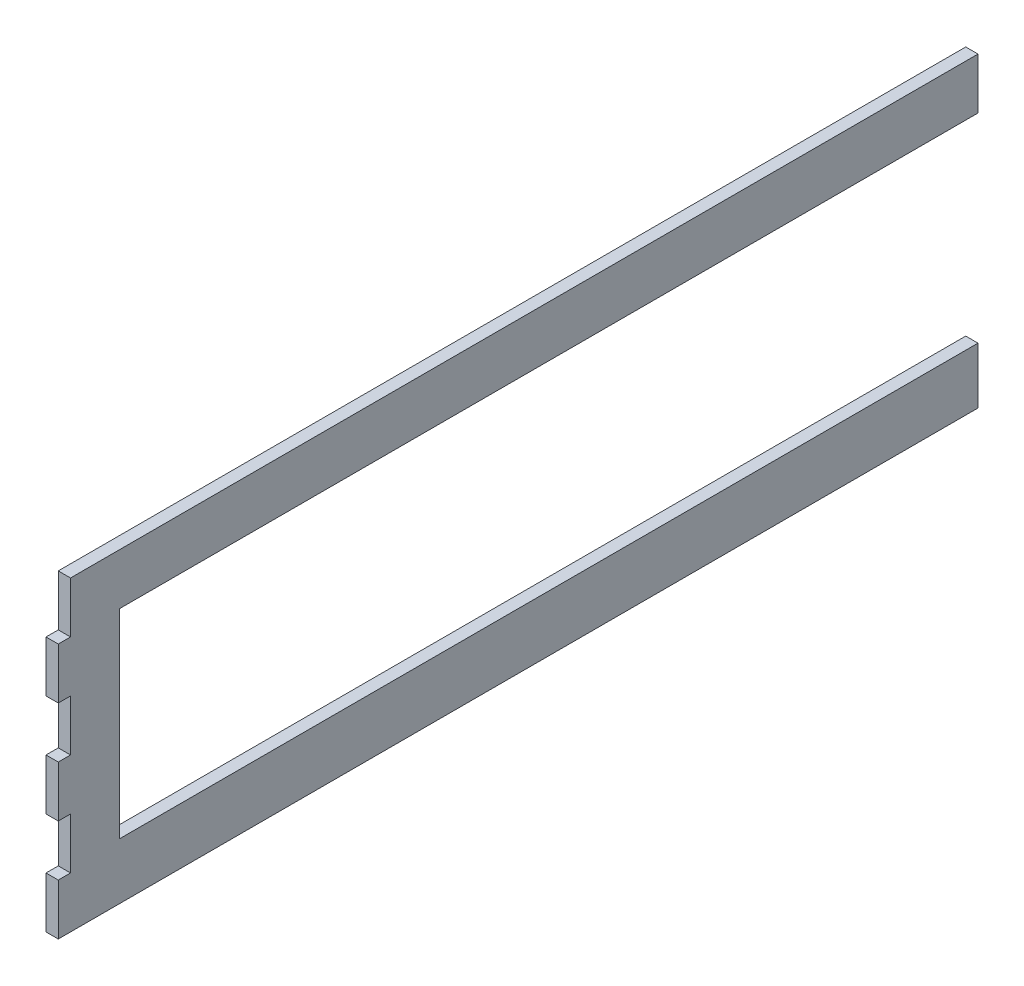
SolidWorks part; units mm, degrees
ref_plane "Front" through (0, 0, 0) normal (0, 0, 1) x (1, 0, 0)
ref_plane "Top" through (0, 0, 0) normal (0, 1, 0) x (1, 0, 0)
ref_plane "Right" through (0, 0, 0) normal (1, 0, 0) x (0, 0, -1)
sketch "Sketch1" plane through (0, 0, 0) normal (1, 0, 0) x (0, 0, -1)
  line L0 (450, 125) -> (450, 150)
  line L1 (0, 0) -> (450, 0)
  line L2 (0, 0) -> (0, 150)
  line L3 (0, 150) -> (450, 150)
  line L4 (450, 0) -> (450, 27.5)
  line L5 (450, 125) -> (30, 125)
  line L7 (450, 27.5) -> (30, 27.5)
  line L8 (30, 125) -> (30, 27.5)
  dimension "D1" = 420
  dimension "D2" = 150
  dimension "D3" = 27.5
  dimension "D4" = 25
  dimension "D5" = 30
extrude "Boss-Extrude1" add sketch "Sketch1" along normal blind 6
sketch "Sketch2" plane through (6, 0, 0) normal (1, 0, 0) x (0, 0, -1)
  line L1 (0, 150) -> (6, 150)
  line L2 (0, 150) -> (0, 125)
  line L3 (0, 125) -> (6, 125)
  line L4 (6, 150) -> (6, 125)
  dimension "D1" = 6
  dimension "D2" = 25
extrude "Cut-Extrude1" cut sketch "Sketch2" against normal blind 6
pattern_linear "LPattern1" count 3 spacing 50 along (0, -1, 0) of "Cut-Extrude1"
